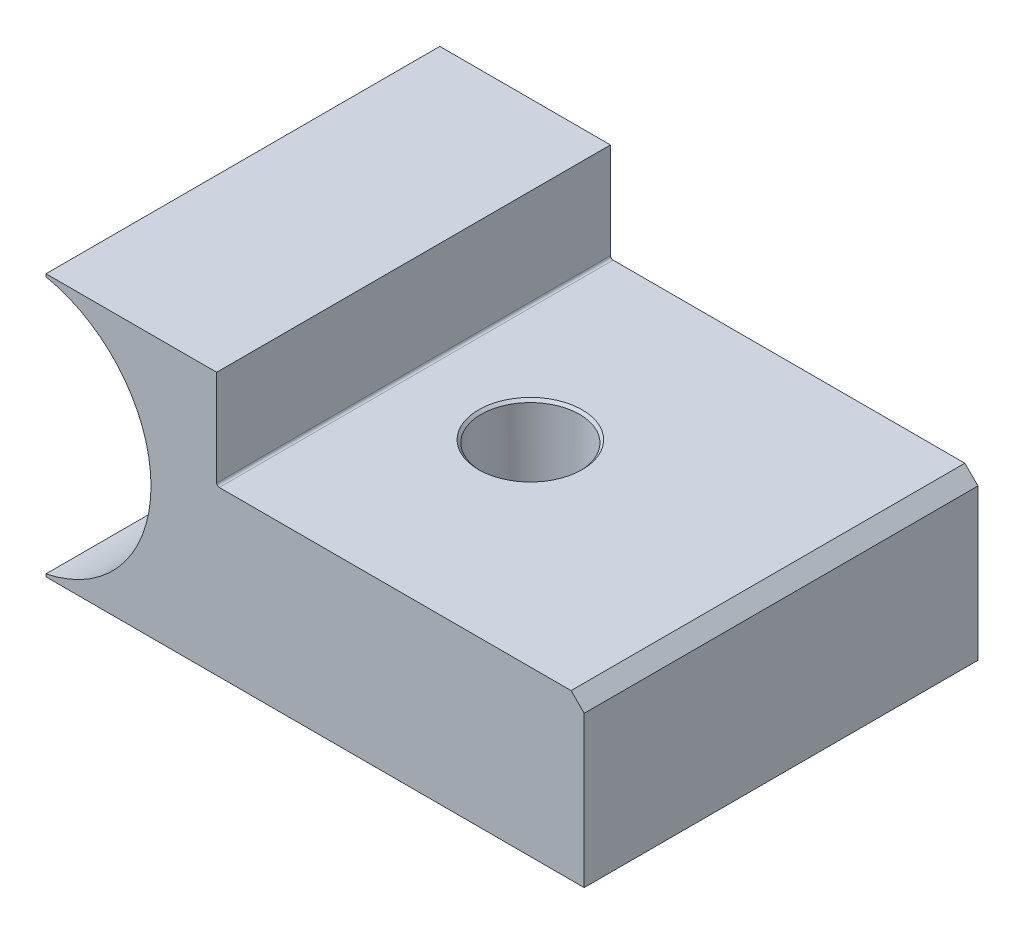
SolidWorks part; units mm, degrees
material "AISI Type A2 Tool Steel Custom"
ref_plane "Front Plane" through (0, 0, 0) normal (0, 0, 1) x (1, 0, 0)
ref_plane "Top Plane" through (0, 0, 0) normal (0, 1, 0) x (1, 0, 0)
ref_plane "Right Plane" through (0, 0, 0) normal (1, 0, 0) x (0, 0, -1)
sketch "Sketch1" plane through (0, 0, 0) normal (0, 0, 1) x (1, 0, 0)
  line L1 (2.54, 0) -> (54.61, 0)
  line L3 (2.54, 25.4) -> (19.05, 25.4)
  line L4 (54.61, 0) -> (54.61, 15.875)
  line L5 (2.54, 25.4) -> (2.54, 25.1434)
  line L6 (19.05, 25.4) -> (19.05, 15.875)
  line L7 (19.05, 15.875) -> (54.61, 15.875)
  line L8 (2.54, 0.2566) -> (2.54, 0)
  arc A1 (2.54, 0.2566) -> (2.54, 25.1434) centre (0, 12.7) ccw
  dimension "D2" = 25.4
  dimension "D1" = 16.51
  dimension "D3" = 9.525
  dimension "D4" = 2.54
  dimension "D5" = 35.56
  dimension "D6" = 15.875
  dimension "D7" = 0.2566
extrude "Boss-Extrude1" add sketch "Sketch1" along normal blind 38.1
sketch "Sketch2" plane through (0, 15.875, 0) normal (0, 1, 0) x (1, 0, 0)
  line L0 (0, -38.1) -> (0, 0) construction
  point P0 (30.353, -19.05)
  point P5 (0, -19.05)
  dimension "D1" = 30.353
hole_wizard "3/8 (0.375) Diameter Hole1" positions "Sketch2" profile "Sketch4" hole size "3/8" standard "ANSI Inch" end condition through all
sketch "Sketch4" plane through (30.353, 15.875, 19.05) normal (1, 0, 0) x (0, 0, 1)
  line L0 (0, 0) -> (0, 15.875)
  line L1 (0, 15.875) -> (4.7625, 15.875)
  line L2 (4.7625, 15.875) -> (4.7625, 0)
  line L5 (4.7625, 0) -> (0, 0)
  line L11 (0, -6.35) -> (0, 107.95) construction
  dimension "Thru Hole Dia." = 9.525
  dimension "Thru Hole Depth" = 15.875
chamfer "Chamfer1" distance 1.27 angle 45 1 edges at (54.61, 15.875, 19.05)
chamfer "Chamfer2" distance 0.254 angle 45 1 edges at (30.353, 15.875, 23.8125)
fillet "Fillet1" radius 0.254 1 edges at (19.05, 15.875, 19.05)
